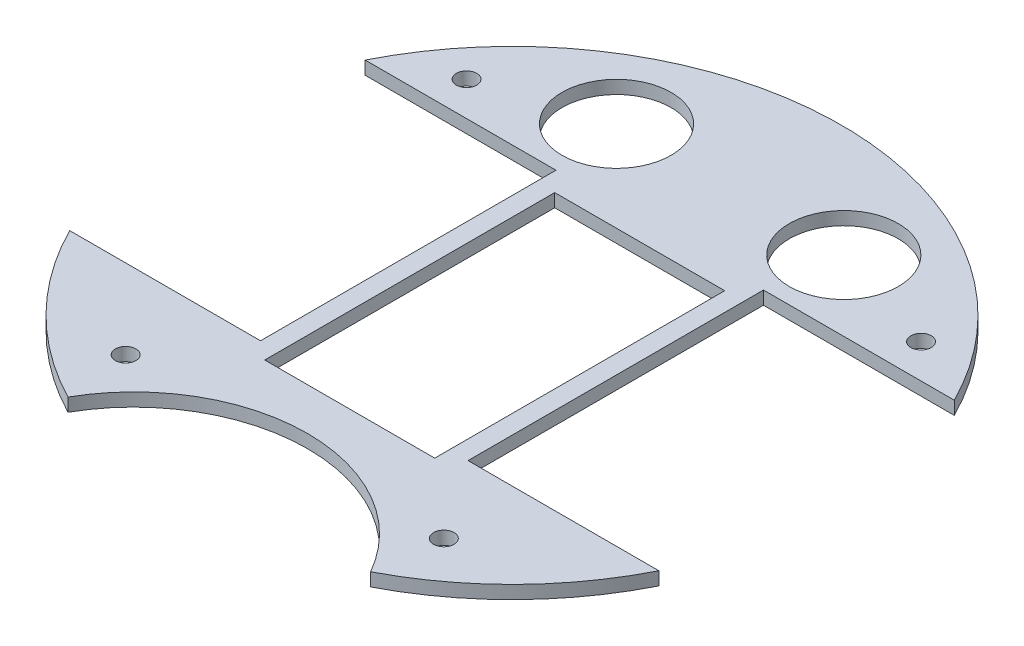
SolidWorks part; units mm, degrees
material "Acrylic (Medium-high impact)"
ref_plane "Front Plane" through (0, 0, 0) normal (0, 0, 1) x (1, 0, 0)
ref_plane "Top Plane" through (0, 0, 0) normal (0, 1, 0) x (1, 0, 0)
ref_plane "Right Plane" through (0, 0, 0) normal (1, 0, 0) x (0, 0, -1)
sketch "Sketch1" plane through (0, 0, 0) normal (0, 1, 0) x (1, 0, 0)
  line L0 (0, -83.2398) -> (-33.2911, -64.4046) construction
  line L1 (0, -83.2398) -> (0, 0) construction
  arc A0 (33.2911, -64.4046) -> (-33.2911, -64.4046) centre (0, 0) ccw
  arc A1 (33.2911, -64.4046) -> (-33.2911, -64.4046) centre (0, -83.2398) ccw
  dimension "D1" = 145
  dimension "D2" = 76.5
  dimension "D3" = 60.5
extrude "Boss-Extrude1" add sketch "Sketch1" along normal blind 2.9
sketch "solenoid placement" plane through (0, 2.9, 0) normal (0, 1, 0) x (1, 0, 0)
  line L4 (-18.7, -35.7) -> (18.7, -35.7)
  line L5 (18.7, -35.7) -> (18.7, 28.1)
  line L6 (18.7, 28.1) -> (-18.7, 28.1)
  line L7 (-18.7, 28.1) -> (-18.7, -35.7)
  line L8 (-18.7, -35.7) -> (18.7, -35.7)
  line L9 (18.7, -35.7) -> (18.7, 28.1)
  line L10 (18.7, 28.1) -> (-18.7, 28.1)
  line L11 (-18.7, 28.1) -> (-18.7, -35.7)
  circle A1 centre (0, 0) radius 72.5 construction
  arc A2 (33.2911, -64.4046) -> (-33.2911, -64.4046) centre (0, 0) ccw construction
  dimension "D1" = 0
extrude "Cut-Extrude1" cut sketch "solenoid placement" against normal through all
sketch "Sketch2" plane through (0, 2.9, 0) normal (0, 1, 0) x (1, 0, 0)
  line L4 (-34.63, -32.5) -> (-22.83, -32.5)
  line L5 (-22.83, -32.5) -> (-22.83, 32.5)
  line L6 (-22.83, 32.5) -> (-64.8074, 32.5)
  line L7 (-64.8074, -32.5) -> (-34.63, -32.5)
  line L8 (-34.63, -32.5) -> (-22.83, -32.5)
  line L9 (-22.83, -32.5) -> (-22.83, 32.5)
  line L10 (-22.83, 32.5) -> (-64.8074, 32.5)
  line L11 (-64.8074, -32.5) -> (-34.63, -32.5)
  line L12 (34.63, -32.5) -> (64.8074, -32.5)
  line L13 (64.8074, 32.5) -> (22.83, 32.5)
  line L14 (22.83, 32.5) -> (22.83, -32.5)
  line L15 (22.83, -32.5) -> (34.63, -32.5)
  line L16 (34.63, -32.5) -> (64.8074, -32.5)
  line L17 (64.8074, 32.5) -> (22.83, 32.5)
  line L18 (22.83, 32.5) -> (22.83, -32.5)
  line L19 (22.83, -32.5) -> (34.63, -32.5)
  arc A2 (-64.8074, 32.5) -> (-64.8074, -32.5) centre (0, 0) ccw
  arc A3 (-64.8074, 32.5) -> (-64.8074, -32.5) centre (0, 0) ccw
  arc A4 (64.8074, -32.5) -> (64.8074, 32.5) centre (0, 0) ccw
  arc A5 (64.8074, -32.5) -> (64.8074, 32.5) centre (0, 0) ccw
  dimension "D2" = 0
  dimension "D1" = 0
extrude "Cut-Extrude2" cut sketch "Sketch2" against normal through all
sketch "Sketch3" plane through (0, 2.9, 0) normal (0, 1, 0) x (1, 0, 0)
  circle A1 centre (25, 48) radius 12
  circle A2 centre (-25, 48) radius 12
  dimension "D1" = 24
extrude "Cut-Extrude3" cut sketch "Sketch3" against normal through all
sketch "Sketch4" plane through (0, 5.8, 0) normal (0, 1, 0) x (1, 0, 0)
  circle A1 centre (35, -50) radius 2.25
  circle A2 centre (35, -50) radius 2.25
  circle A3 centre (-35, -50) radius 2.25
  circle A4 centre (-35, -50) radius 2.25
  circle A5 centre (-50, 40) radius 2.25
  circle A6 centre (-50, 40) radius 2.25
  circle A7 centre (50, 40) radius 2.25
  circle A8 centre (50, 40) radius 2.25
  dimension "D1" = 0
  dimension "D2" = 0
  dimension "D3" = 0
  dimension "D4" = 0
extrude "Cut-Extrude4" cut sketch "Sketch4" against normal through all
equation "\"smallPulleyTeeth\"= 15"
equation "\"largePulleyTeeth\"= 30"
equation "\"eighthThick\"= 2.9mm"
equation "\"sixteenthThick\" = 1.7mm"
equation "\"quarterThick\"=5.9mm"
equation "\"OD\" = 145mm"
equation "\"puckAngle\" = 60.5deg"
equation "\"D1@Sketch1\"=\"OD\""
equation "\"puckDiam\" = 76.5mm"
equation "\"D2@Sketch1\"=\"puckDiam\""
equation "\"D3@Sketch1\"=\"puckAngle\""
equation "\"D1@Boss-Extrude1\"=\"eighthThick\""
equation "\"axlePress\" = 5.9mm"
equation "\"press\" = 0.2mm"
equation "\"wheelClear\" = 0.3mm"
equation "\"10-32clear\" = 4.5mm"
equation "\"6-32clear\" = 3.3mm"
equation "\"8-32clear\" = 4.0mm"
equation "\"wheelHeight\" = 22mm"
equation "\"wheelWell\" = 65mm"
